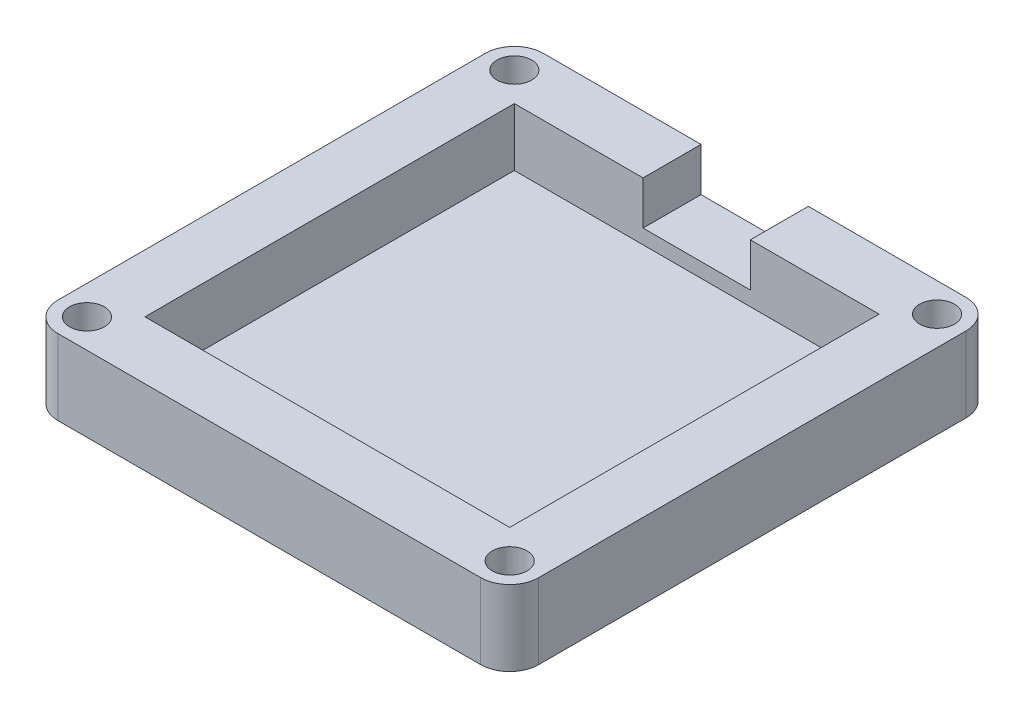
SolidWorks part; units mm, degrees
ref_plane "Front Plane" through (0, 0, 0) normal (0, 0, 1) x (1, 0, 0)
ref_plane "Top Plane" through (0, 0, 0) normal (0, 1, 0) x (1, 0, 0)
ref_plane "Right Plane" through (0, 0, 0) normal (1, 0, 0) x (0, 0, -1)
sketch "Sketch1" plane through (0, 0, 0) normal (0, 1, 0) x (1, 0, 0)
  line L1 (-65.3647, -33.0202) -> (-2.4647, -33.0202)
  line L2 (-65.3647, -33.0202) -> (-65.3647, 30.6798)
  line L3 (-65.3647, 30.6798) -> (-2.4647, 30.6798)
  line L4 (-2.4647, -33.0202) -> (-2.4647, 30.6798)
  line L5 (-65.3647, -33.0202) -> (-2.4647, 30.6798) construction
  line L6 (-65.3647, 30.6798) -> (-2.4647, -33.0202) construction
  line L7 (-75.3647, 40.6798) -> (7.5353, 40.6798)
  line L8 (-75.3647, 40.6798) -> (-75.3647, -43.0202)
  line L9 (-75.3647, -43.0202) -> (7.5353, -43.0202)
  line L10 (7.5353, 40.6798) -> (7.5353, -43.0202)
  line L11 (-75.3647, 40.6798) -> (7.5353, -43.0202) construction
  line L12 (-75.3647, -43.0202) -> (7.5353, 40.6798) construction
  circle A1 centre (-70.3647, -38.0202) radius 1.7
  circle A2 centre (2.5353, -38.0202) radius 1.7
  circle A3 centre (2.5353, 35.6798) radius 1.7
  circle A4 centre (-70.3647, 35.6798) radius 1.7
  circle A5 centre (2.5353, 35.6798) radius 3
  circle A6 centre (-70.3647, 35.6798) radius 3
  circle A7 centre (-70.3647, -38.0202) radius 3
  circle A8 centre (2.5353, -38.0202) radius 3
  point P0 (-33.7647, -1.5702)
  point P5 (-33.9147, -1.1702)
  dimension "D5" = 3.4
  dimension "D7" = 5
  dimension "D6" = 5
  dimension "D8" = 5
  dimension "D9" = 5
  dimension "D10" = 3.4
  dimension "D13" = 5
  dimension "D14" = 5
  dimension "D15" = 5
  dimension "D16" = 5
  dimension "D17" = 3.4
  dimension "D18" = 3.4
  dimension "D19" = 6
  dimension "D20" = 6
  dimension "D21" = 6
  dimension "D22" = 6
  dimension "D1" = 63.7
  dimension "D2" = 62.9
  dimension "D3" = 82.9
  dimension "D4" = 83.7
  dimension "D11" = 10
  dimension "D12" = 10
extrude "Boss-Extrude1" add sketch "Sketch1" along normal blind 13 contours L10 L7 L8 L9 A8 A7 A6 A5 L4 L1 L2 L3 region at (-33.9147, 0, -39.5017)
extrude "Boss-Extrude2" add sketch "Sketch1<4>" along normal blind 3 contours L1 L4 L3 L2 region at (-33.9147, 0, 1.1702)
sketch "Sketch1<4>" plane through (0, 0, 0) normal (0, 1, 0) x (1, 0, 0) same geometry as "Sketch1"
sketch "Sketch2" plane through (0, 13, 0) normal (0, 1, 0) x (1, 0, 0)
  line L0 (-43.1647, 40.6798) -> (-43.1647, 30.6798)
  line L1 (-43.1647, 40.6798) -> (-24.6647, 40.6798)
  line L2 (-43.1647, 30.6798) -> (-24.6647, 30.6798)
  line L3 (-24.6647, 40.6798) -> (-24.6647, 30.6798)
  line L4 (-75.3647, 40.6798) -> (7.5353, 40.6798) construction
  line L5 (-65.3647, 30.6798) -> (-2.4647, 30.6798) construction
  line L7 (-75.3647, 40.6798) -> (-75.3647, -43.0202) construction
  dimension "D1" = 18.5
  dimension "D2" = 32.2
extrude "Cut-Extrude1" cut sketch "Sketch2" against normal blind 7.5
fillet "Fillet1" radius 5 4 edges at (7.5353, 6.5, 43.0202) (-75.3647, 6.5, 43.0202) (7.5353, 6.5, -40.6798) (-75.3647, 6.5, -40.6798)
